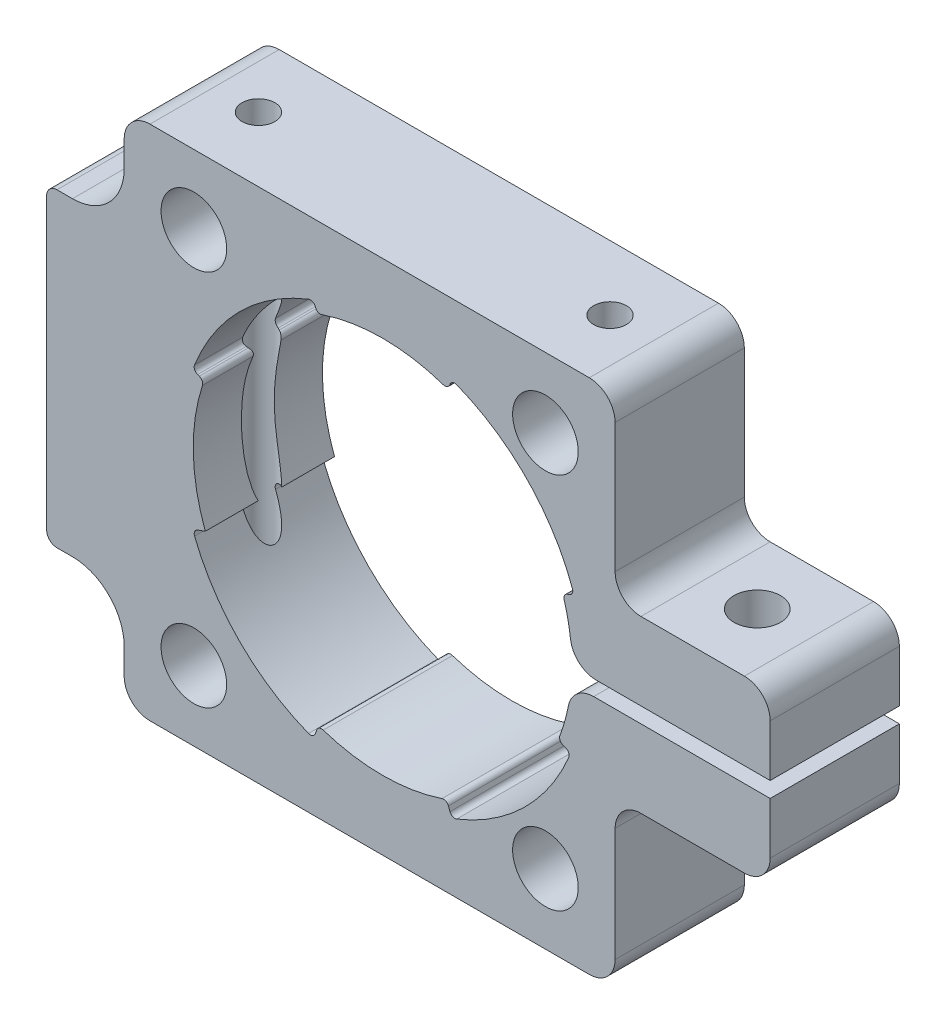
SolidWorks part; units mm, degrees
ref_plane "Front Plane" through (0, 0, 0) normal (0, 0, 1) x (1, 0, 0)
ref_plane "Top Plane" through (0, 0, 0) normal (0, 1, 0) x (1, 0, 0)
ref_plane "Right Plane" through (0, 0, 0) normal (1, 0, 0) x (0, 0, -1)
sketch "Sketch1" plane through (0, 0, 0) normal (0, 0, 1) x (1, 0, 0)
  line L0 (36.6249, 0.3887) -> (74.9917, 0.3887)
  line L1 (44.9917, -22.6113) -> (44.9917, -44.6113)
  line L2 (39.9917, 50.3887) -> (-45.0083, 50.3887)
  line L3 (-50.0083, 45.3887) -> (-50.0083, -44.6113)
  line L4 (-45.0083, -49.6113) -> (39.9917, -49.6113)
  line L5 (-48.5438, 48.9242) -> (-45.0083, 45.3887) construction
  line L6 (74.9917, -2.6113) -> (36.5019, -2.6113)
  line L7 (-0.0083, 0.3887) -> (-0.0083, 50.3887) construction
  line L8 (-0.0083, 0.3887) -> (-50.0083, 0.3887) construction
  line L9 (49.9917, 15.3887) -> (69.9917, 15.3887)
  line L10 (74.9917, 10.3887) -> (74.9917, 0.3887)
  line L11 (69.9917, -17.6113) -> (49.9917, -17.6113)
  line L12 (44.9917, 45.3887) -> (44.9917, 20.3887)
  line L13 (74.9917, -2.6113) -> (74.9917, -12.6113)
  line L14 (-45.0083, 45.3887) -> (-36.523, 36.9034) construction
  line L15 (43.5273, 48.9242) -> (39.9917, 45.3887) construction
  line L16 (39.9917, 45.3887) -> (31.5065, 36.9034) construction
  line L17 (43.5273, -48.1469) -> (39.9917, -44.6113) construction
  line L18 (39.9917, -44.6113) -> (31.5065, -36.126) construction
  line L19 (-48.5438, -48.1469) -> (-45.0083, -44.6113) construction
  line L20 (-45.0083, -44.6113) -> (-36.523, -36.126) construction
  arc A0 (36.5019, -2.6113) -> (36.6249, 0.3887) centre (-0.0083, 0.3887) cw
  arc A1 (39.9917, 50.3887) -> (44.9917, 45.3887) centre (39.9917, 45.3887) cw
  arc A2 (44.9917, -44.6113) -> (39.9917, -49.6113) centre (39.9917, -44.6113) cw
  arc A3 (-45.0083, 50.3887) -> (-50.0083, 45.3887) centre (-45.0083, 45.3887) ccw
  arc A4 (-50.0083, -44.6113) -> (-45.0083, -49.6113) centre (-45.0083, -44.6113) ccw
  arc A5 (44.9917, -22.6113) -> (49.9917, -17.6113) centre (49.9917, -22.6113) cw
  arc A6 (69.9917, -17.6113) -> (74.9917, -12.6113) centre (69.9917, -12.6113) ccw
  arc A7 (69.9917, 15.3887) -> (74.9917, 10.3887) centre (69.9917, 10.3887) cw
  arc A8 (44.9917, 20.3887) -> (49.9917, 15.3887) centre (49.9917, 20.3887) ccw
  circle A9 centre (-36.523, 36.9034) radius 6.35
  circle A10 centre (31.5065, 36.9034) radius 6.35
  circle A11 centre (31.5065, -36.126) radius 6.35
  circle A12 centre (-36.523, -36.126) radius 6.35
  point P18 (-50.0083, -49.6113)
  point P21 (49.9917, -49.6113)
  point P25 (44.9917, -17.6113)
  dimension "D1" = 36.6332
  dimension "D4" = 45
  dimension "D7" = 5
  dimension "D10" = 5
  dimension "D11" = 12.7
  dimension "D2" = 100
  dimension "D3" = 3
  dimension "D5" = 50
  dimension "D6" = 15
  dimension "D8" = 100
  dimension "D9" = 30
  dimension "D12" = 12
extrude "Boss-Extrude1" add sketch "Sketch1" against normal blind 25
sketch "Sketch3" plane through (0, -17.6113, 0) normal (0, -1, 0) x (1, 0, 0)
  line L0 (59.9917, -25) -> (59.9917, -12.5) construction
  line L1 (49.9917, -25) -> (69.9917, -25) construction
  line L2 (59.9917, -12.5) -> (59.9917, 0) construction
  line L3 (49.9917, 0) -> (69.9917, 0) construction
  circle A0 centre (59.9917, -12.5) radius 5
  dimension "D1" = 10
extrude "Cut-Extrude2" cut sketch "Sketch3" against normal up to next
hole_wizard "M10x1.0 Tapped Hole1" positions "Sketch8" profile "Sketch9" tap size "M10x1.0" standard "ANSI Metric" end condition through all
sketch "Sketch8" plane through (0, 15.3887, 0) normal (0, 1, 0) x (1, 0, 0)
  point P0 (59.9917, 12.5)
  point P6 (59.9917, 12.5)
sketch "Sketch9" plane through (59.9917, 15.3887, -12.5) normal (1, 0, 0) x (0, 0, 1)
  line L0 (0, 0) -> (0, 65)
  line L1 (0, 65) -> (4.5, 65)
  line L2 (4.5, 65) -> (4.5, 0)
  line L5 (4.5, 0) -> (0, 0)
  line L11 (0, -6.35) -> (0, 107.95) construction
  dimension "Thru Tap Drill Dia." = 9
  dimension "Thru Tap Drill Depth" = 65
cosmetic thread "Hole Thread1" parameters "D2"=10
cosmetic thread "Hole Thread6" parameters "D2"=10
hole_wizard "1/4 (0.25) Diameter Hole1" positions "Sketch14" profile "Sketch13" hole size "1/4" standard "ANSI Inch" end condition through all
sketch "Sketch14" plane through (0, 50.3887, 0) normal (0, 1, 0) x (1, 0, 0)
  line L0 (-30.173, 0) -> (-42.873, 0) construction
  line L4 (25.1565, 0) -> (37.8565, 0) construction
  line L8 (31.5065, 0) -> (31.5065, 12.5) construction
  line L10 (-36.523, 0) -> (-36.523, 12.5) construction
  line L12 (49.9917, 0) -> (69.9917, 0) construction
  line L13 (-50.0083, 0) -> (-45.0083, 0) construction
  line L14 (31.5065, 12.5) -> (-36.523, 12.5) construction
  line L15 (-36.523, 12.5) -> (-50.0083, 12.5) construction
  line L16 (-50.0083, 25) -> (-50.0083, 0) construction
  point P0 (31.5065, 12.5)
  point P2 (-36.523, 12.5)
sketch "Sketch13" plane through (31.5065, 50.3887, -12.5) normal (1, 0, 0) x (0, 0, 1)
  line L0 (0, 0) -> (0, 100)
  line L1 (0, 100) -> (3.175, 100)
  line L2 (3.175, 100) -> (3.175, 0)
  line L5 (3.175, 0) -> (0, 0)
  line L11 (0, -6.35) -> (0, 107.95) construction
  dimension "Thru Hole Dia." = 6.35
  dimension "Thru Hole Depth" = 100
sketch "Sketch15" plane through (-50.0083, 0, 0) normal (-1, 0, 0) x (0, 0, 1)
  line L0 (-25, 45.3887) -> (-25, -44.6113) construction
  line L1 (-25, -29.6113) -> (0, -29.6113)
  line L2 (-25, -29.6113) -> (-25, 30.3887)
  line L3 (-25, 30.3887) -> (0, 30.3887)
  line L4 (0, -29.6113) -> (0, 30.3887)
  line L5 (0, 45.3887) -> (0, -44.6113) construction
  line L6 (-25, 0) -> (-12.5, 0) construction
  line L7 (-12.5, 0) -> (0, 0) construction
  line L10 (-12.5, 0) -> (-12.5, 20) construction
  line L11 (-12.5, 0) -> (-12.5, -20) construction
  line L12 (-12.5, 30.3887) -> (-12.5, 45.3887) construction
  line L13 (-25, 45.3887) -> (0, 45.3887) construction
  line L14 (-12.5, -29.6113) -> (-12.5, -44.6113) construction
  line L15 (-25, -44.6113) -> (0, -44.6113) construction
  circle A0 centre (-12.5, 0) radius 2.5
  circle A1 centre (-12.5, 20) radius 2.5
  circle A2 centre (-12.5, -20) radius 2.5
  dimension "D1" = 5
  dimension "D2" = 40
  dimension "D3" = 60
extrude "Boss-Extrude2" add sketch "Sketch15" along normal blind 15
fillet "Fillet1" radius 10 2 edges at (-50.0083, 30.3887, -12.5) (-50.0083, -29.6113, -12.5)
fillet "Fillet2" radius 2 2 edges at (-65.0083, -29.6113, -12.5) (-65.0083, 30.3887, -12.5)
sketch "Sketch16" plane through (0, 0, -25) normal (0, 0, -1) x (-1, 0, 0)
  line L0 (-12.6531, 34.7642) -> (-13.0298, 35.799)
  line L1 (12.6551, 34.7696) -> (13.0298, 35.799)
  line L2 (34.5545, 12.5768) -> (35.799, 13.0298)
  line L3 (34.3046, -12.4858) -> (35.799, -13.0298)
  line L5 (12.4052, -34.0831) -> (13.0298, -35.799)
  line L6 (-36.1172, 12.1197) -> (-34.838, 11.6905)
  line L8 (-35.4578, -13.9314) -> (-33.9548, -13.3409)
  line L9 (0, 0) -> (0, 39.1096) construction
  line L10 (0, 0) -> (39.1096, 0) construction
  line L11 (0, 0) -> (0, -39.1096) construction
  line L12 (0, 0) -> (-39.0971, -0.9896) construction
  line L13 (-36.4007, -14.3019) -> (-39.0971, -0.9896) construction
  line L14 (-39.0971, -0.9896) -> (-37.0777, 12.442) construction
  line L15 (-13.3763, 36.751) -> (0, 39.1096) construction
  line L16 (0, 39.1096) -> (13.3763, 36.751) construction
  line L17 (36.751, -13.3763) -> (39.1096, 0) construction
  line L18 (39.1096, 0) -> (36.751, 13.3763) construction
  line L19 (-13.3763, -36.751) -> (0, -39.1096) construction
  line L20 (0, -39.1096) -> (13.3763, -36.751) construction
  line L21 (-12.4033, -34.0779) -> (-13.0298, -35.799)
  arc A0 (14.336, -36.3873) -> (36.3873, -14.336) centre (0, 0) ccw
  arc A1 (-36.5019, -2.6113) -> (-36.6249, 0.3887) centre (0.0083, 0.3887) ccw construction
  arc A2 (34.5545, 12.5768) -> (12.6551, 34.7696) centre (0.0083, 0.3887) ccw
  arc A3 (-33.9548, -13.3409) -> (-12.4033, -34.0779) centre (0.0083, 0.3887) ccw
  arc A4 (12.4052, -34.0831) -> (34.3046, -12.4858) centre (0.0083, 0.3887) ccw
  arc A5 (-36.0129, -15.2522) -> (-14.336, -36.3873) centre (0, 0) ccw
  arc A6 (-14.336, 36.3873) -> (-36.7384, 13.4107) centre (0, 0) ccw
  arc A7 (-12.6531, 34.7642) -> (-34.838, 11.6905) centre (0.0083, 0.3887) ccw
  arc A8 (-36.7384, 13.4107) -> (-36.1172, 12.1197) centre (-35.7991, 13.0678) ccw
  arc A9 (-36.0129, -15.2522) -> (-35.4578, -13.9314) centre (-35.0921, -14.8622) cw
  arc A10 (-14.336, -36.3873) -> (-13.0298, -35.799) centre (-13.9694, -35.4569) ccw
  arc A11 (14.336, -36.3873) -> (13.0298, -35.799) centre (13.9694, -35.4569) cw
  arc A12 (14.336, 36.3873) -> (13.0298, 35.799) centre (13.9694, 35.4569) ccw
  arc A13 (-14.336, 36.3873) -> (-13.0298, 35.799) centre (-13.9694, 35.4569) cw
  arc A14 (36.3873, 14.336) -> (14.336, 36.3873) centre (0, 0) ccw
  arc A15 (36.3873, -14.336) -> (35.799, -13.0298) centre (35.4569, -13.9694) ccw
  arc A16 (36.3873, 14.336) -> (35.799, 13.0298) centre (35.4569, 13.9694) cw
  dimension "D2" = 1
  dimension "D3" = 1
  dimension "D1" = 40
extrude "Cut-Extrude4" cut sketch "Sketch16" against normal through all
fillet "Fillet3" radius 1 8 edges at (-12.4052, -34.0831, -12.5) (12.4033, -34.0779, -12.5) (33.9548, -13.3409, -5.2393) (-34.5545, 12.5768, -5.0045) (-34.5545, 12.5768, -19.9955) (-12.6551, 34.7696, -12.5) (12.6531, 34.7642, -12.5) (34.838, 11.6905, -12.5)
fillet "Fillet4" radius 5 2 edges at (36.5019, -2.6113, -12.5) (36.6249, 0.3887, -12.5)
